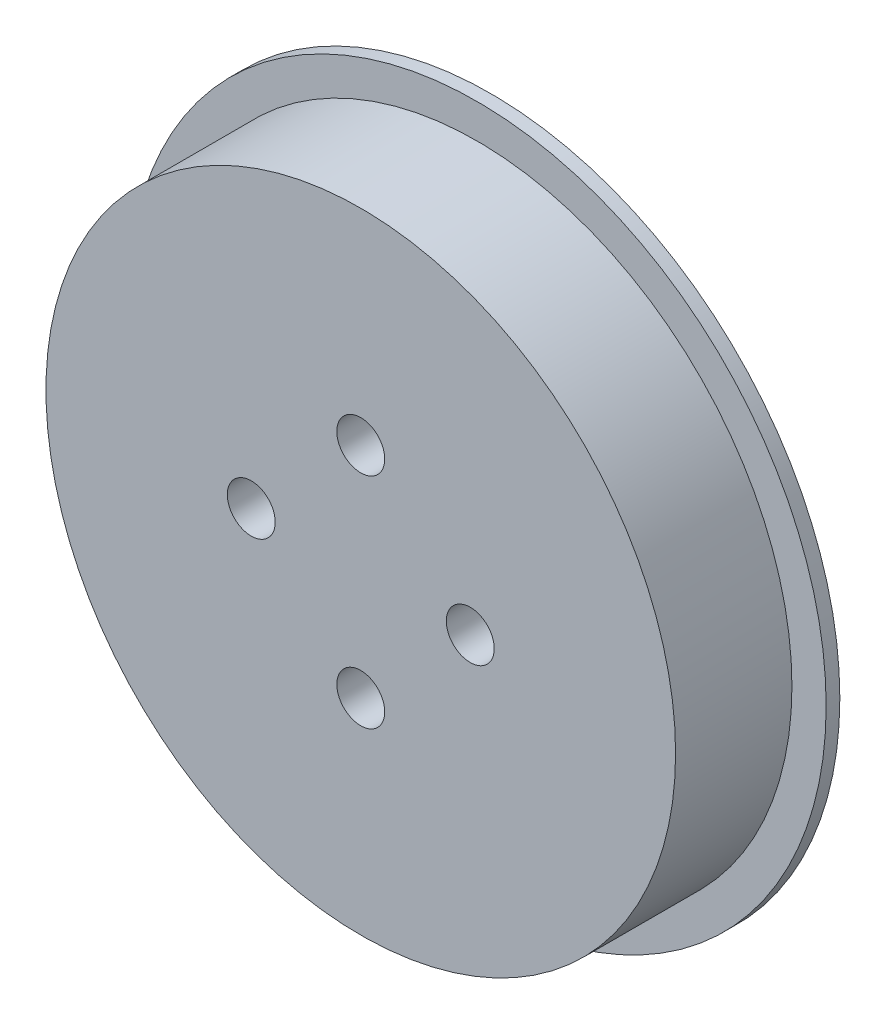
SolidWorks part; units mm, degrees
ref_plane "Front Plane" through (0, 0, 0) normal (0, 0, 1) x (1, 0, 0)
ref_plane "Top Plane" through (0, 0, 0) normal (0, 1, 0) x (1, 0, 0)
ref_plane "Right Plane" through (0, 0, 0) normal (1, 0, 0) x (0, 0, -1)
sketch "Sketch1" plane through (0, 0, 0) normal (0, 0, 1) x (1, 0, 0)
  line L0 (0, 0) -> (0, 8) construction
  circle A0 centre (0, 0) radius 25.5
  circle A1 centre (0, 0) radius 23
  circle A2 centre (0, 0) radius 12.5
  circle A3 centre (0, 8) radius 1.75
  circle A4 centre (8, 0) radius 1.75
  circle A5 centre (0, -8) radius 1.75
  circle A6 centre (-8, 0) radius 1.75
  point P5 (0, 8)
  dimension "D1" = 51
  dimension "D2" = 46
  dimension "D3" = 25
  dimension "D5" = 3.5
  dimension "D4" = 8
  dimension "D6" = 4
extrude "Boss-Extrude1" add sketch "Sketch1" along normal blind 9.5 contours A1 A2 | A2 A6 A5 A4 A3 region at (-22.3495, 0, 0) region at (0, 0, 0)
extrude "Boss-Extrude2" add sketch "Sketch1<3>" along normal blind 1 contours A0 A1 region at (-24.7788, 0, 0)
sketch "Sketch1<3>" plane through (0, 0, 0) normal (0, 0, 1) x (1, 0, 0) same geometry as "Sketch1"
extrude "Cut-Extrude1" cut sketch "Sketch1<4>" along normal blind 5 contours A2 A6 A5 A4 A3 region at (0, 0, 0)
sketch "Sketch1<4>" plane through (0, 0, 0) normal (0, 0, 1) x (1, 0, 0) same geometry as "Sketch1"
